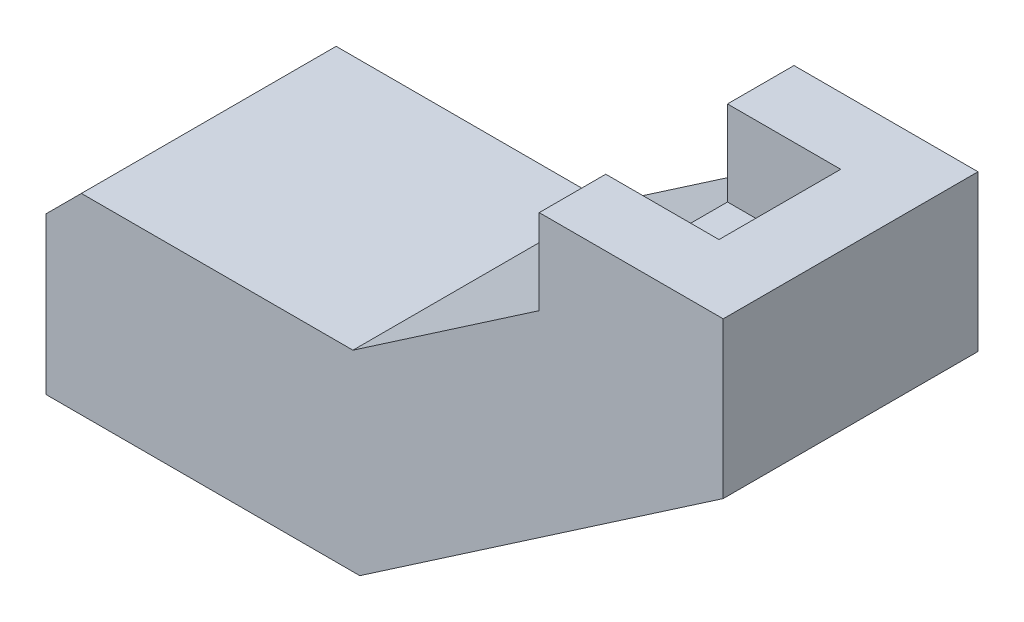
SolidWorks part; units mm, degrees
note: '?' marks a value the reader was unsure of.
ref_plane "Front Plane" through (0, 0, 0) normal (0, 0, 1) x (1, 0, 0)
ref_plane "Top Plane" through (0, 0, 0) normal (0, 1, 0) x (1, 0, 0)
ref_plane "Right Plane" through (0, 0, 0) normal (1, 0, 0) x (0, 0, -1)
sketch "Sketch1" plane through (0, 0, 0) normal (0, 0, 1) x (1, 0, 0)
  line L0 (0, 6) -> (5, 6)
  line L1 (5, 6) -> (5, -5)
  line L2 (-20.6795, -22.5563) -> (-49.0563, -22.5563)
  line L4 (-49.0563, -22.5563) -> (-60.5563, -11.0563)
  line L5 (-60.5563, -11.0563) -> (-46.4142, 3.0858)
  line L6 (-46.4142, 3.0858) -> (-34.3284, -9)
  line L7 (-34.3284, -9) -> (-21.1642, -9)
  line L8 (-8, -9) -> (-8, 0) construction
  line L9 (0, 0) -> (-30, 0) construction
  line L10 (-8, 0) -> (0, 0)
  line L11 (0, 0) -> (0, 6)
  line L12 (-39.25, -1.25) -> (-54.8063, -16.8063) construction
  line L13 (-45, 4.5) -> (-46.4142, 3.0858) construction
  line L14 (-33.5, -7) -> (-54.8063, -16.8063) construction
  line L15 (-54.8063, -16.8063) -> (-45, 4.5) construction
  line L16 (-8, 0) -> (-21.1642, -9)
  line L17 (5, -5) -> (-20.6795, -22.5563)
  line L18 (-8, -9) -> (-8, -17) construction
  line L19 (-33.5, -7) -> (-45, 4.5) construction
  line L20 (5, -17) -> (-8, -17) construction
  line L21 (-33.5, -7) -> (-45, 4.5) construction
  line L22 (-8, -17) -> (-20.6795, -22.5563) construction
  line L23 (5, -5) -> (5, -17) construction
  line L24 (-21.1642, -9) -> (-8, -9) construction
  line L25 (0, 0) -> (-30, 0) construction
  dimension "D1" = 2
  dimension "D2" = 8
  dimension "D3" = 2
  dimension "D4" = 20
  dimension "D5" = 8
  dimension "D6" = 5
  dimension "D7" = 11
extrude "Boss-Extrude1" add sketch "Sketch1" against normal blind 13 and the other way blind 5
sketch "Sketch2" plane through (0, 0, 0) normal (0, 1, 0) x (1, 0, 0)
  circle A0 centre (-3, 3.95) radius 1.5
  circle A1 centre (-3, 3.95) radius 1.5 construction
extrude "Cut-Extrude1" cut sketch "Sketch2" against normal through all
sketch "Sketch4" plane through (0, 0, 0) normal (0, 1, 0) x (1, 0, 0)
  line L0 (0, -5) -> (0, 13) construction
  line L1 (-8, -5) -> (0, -5)
  line L2 (-8, -5) -> (-8, -0.3)
  line L3 (-8, -0.3) -> (0, -0.3)
  line L4 (0, -5) -> (0, -0.3)
  line L5 (0, 0) -> (-30, 0) construction
  line L6 (-8, 13) -> (0, 13)
  line L7 (-8, 13) -> (-8, 8.3)
  line L8 (-8, 8.3) -> (0, 8.3)
  line L9 (0, 13) -> (0, 8.3)
  line L10 (-8, -5) -> (-8, 13) construction
  line L11 (0, -5) -> (-8, -5) construction
  dimension "D1" = 0.3
extrude "Boss-Extrude2" add sketch "Sketch4" along normal up to surface (6 mm away) up to face at (2.5, 6, -4)
sketch "Sketch5" plane through (0, 0, 0) normal (0, 1, 0) x (1, 0, 0)
  line L0 (-1.2679, 0.95) -> (-4.7321, 0.95)
  line L1 (-4.7321, 0.95) -> (-6.4641, 3.95)
  line L2 (-6.4641, 3.95) -> (-4.7321, 6.95)
  line L3 (-4.7321, 6.95) -> (-1.2679, 6.95)
  line L4 (-1.2679, 6.95) -> (0.4641, 3.95)
  line L5 (0.4641, 3.95) -> (-1.2679, 0.95)
  circle A0 centre (-3, 3.95) radius 3.4641 construction
  circle A1 centre (-3, 3.95) radius 1.5 construction
  dimension "D1" = 6
extrude "Cut-Extrude3" cut sketch "Sketch5" against normal through all from offset 5 offset against normal yes
sketch "Sketch6" plane through (0, 0, 5) normal (0, 0, 1) x (1, 0, 0)
  line L2 (-60.5563, -11.0563) -> (-49.0563, -22.5563) construction
  line L10 (-54.8063, -16.8063) -> (-30.3048, 7.6952) construction
  line L11 (-33.5, -7) -> (-45, 4.5) construction
  line L12 (-53.1, -15.1) -> (-25.85, -15.1) construction
  line L13 (-45.997, -12) -> (-25.85, -12) construction
  line L14 (-45.997, -12) -> (-45.997, -18.2) construction
  line L15 (-45.997, -18.2) -> (-25.85, -18.2) construction
  line L16 (-25.85, -12) -> (-25.85, -18.2) construction
  line L17 (-53.1, -15.1) -> (-60.85, -15.1) construction
  line L18 (0, 0) -> (-30, 0) construction
  line L19 (-21.1642, -9) -> (-34.3284, -9) construction
  line L20 (-42.85, -22.5563) -> (-49.0563, -22.5563)
  line L21 (-49.0563, -22.5563) -> (-20.6795, -22.5563) construction
  line L22 (-49.0563, -22.5563) -> (-60.5563, -11.0563)
  line L23 (-46.4142, 3.0858) -> (-60.5563, -11.0563) construction
  line L24 (-60.5563, -11.0563) -> (-46.4142, 3.0858)
  line L25 (-46.4142, 3.0858) -> (-45.85, 2.5216)
  line L26 (-34.3284, -9) -> (-46.4142, 3.0858) construction
  line L27 (-42.85, -9) -> (-42.85, -22.5563)
  line L28 (-34.3284, -9) -> (-42.85, -9)
  line L29 (-46.4142, 3.0858) -> (-34.3284, -9)
  circle A0 centre (-53.1, -15.1) radius 7.75 construction
  dimension "D1" = 15.5
  dimension "D2" = 6.2
  dimension "D3" = 35
  dimension "D4" = 3
  dimension "D5" = 17
extrude "Cut-Extrude4" cut sketch "Sketch6" against normal through all
ref_axis "Axis1" through (-3, -5, -3.95) along (0, 1, 0)?
ref_plane "Plane1" through (0, 0, -3.95) normal (0, 0, 1) x (1, 0, 0)
sketch "Sketch7" plane through (0, 0, -3.95) normal (0, 0, 1) x (1, 0, 0)
  line L0 (-45.997, -12) -> (-45.997, -18.2) construction
  line L1 (-25.85, -12) -> (-25.85, -18.2) construction
  line L4 (-45.997, -18.2) -> (-25.85, -18.2) construction
  line L5 (-45.997, -12) -> (-45.997, -15.1)
  line L6 (-25.85, -12.35) -> (-25.85, -15.1) construction
  line L7 (-45.997, -12) -> (-39.7903, -12)
  line L8 (-45.997, -15.1) -> (-25.85, -15.1)
  line L9 (-45.997, -18.2) -> (-25.85, -18.2) construction
  line L10 (-39.7903, -12) -> (-25.85, -12) construction
  line L11 (-25.85, -15.1) -> (-25.85, -18.2) construction
  line L12 (-45.997, -15.1) -> (-45.997, -18.2) construction
  line L13 (-53.2914, -15.1) -> (-45.997, -15.1) construction
  line L14 (-38.2903, -12.35) -> (-25.85, -12.35)
  line L15 (-46.2903, -11.4) -> (-43.2903, -11.4)
  line L16 (-43.2903, -11.4) -> (-43.2903, -12)
  line L17 (-43.2903, -12) -> (-39.7903, -12)
  line L18 (-39.7903, -12) -> (-38.2903, -12.35)
  line L19 (-25.85, -12) -> (-25.85, -12.35) construction
  line L20 (-53.1, -15.1) -> (-25.85, -15.1) construction
  line L21 (-25.85, -12.35) -> (-24.85, -12.85)
  line L22 (-24.85, -12.85) -> (-24.85, -15.1)
  line L23 (-24.85, -15.1) -> (-25.85, -15.1)
  circle A2 centre (-53.1, -15.1) radius 7.75 construction
  dimension "D1" = 3.5
  dimension "D2" = 3
  dimension "D3" = 3.7
  dimension "D4" = 3.1
  dimension "D5" = 2.75
  dimension "D6" = 1.5
  dimension "D7" = 1
  dimension "D8" = 0.5
revolve "Cut-Revolve1" cut sketch "Sketch7" angle 360 about L8
chamfer "Chamfer1" distance 2.5 angle 45 1 edges at (-42.85, -9, -4)
